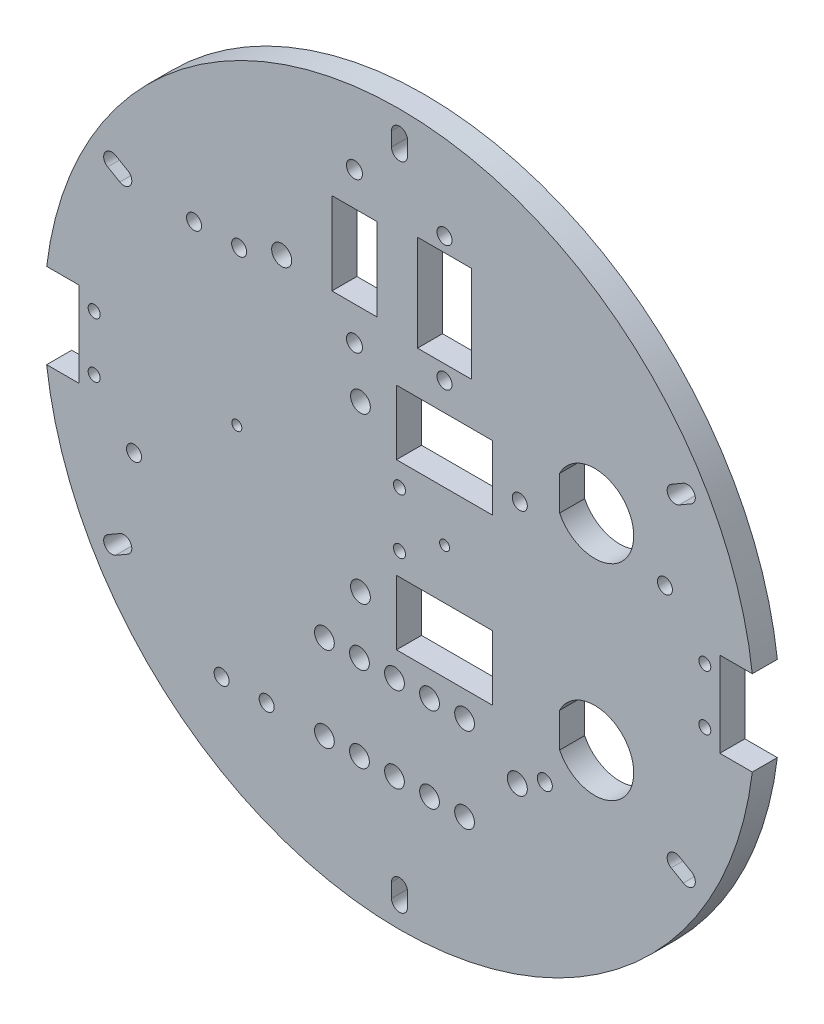
SolidWorks part; units mm, degrees
material "Alliage 1060"
ref_plane "Plan de face" through (0, 0, 0) normal (0, 0, 1) x (1, 0, 0)
ref_plane "Plan de dessus" through (0, 0, 0) normal (0, 1, 0) x (1, 0, 0)
ref_plane "Plan de droite" through (0, 0, 0) normal (1, 0, 0) x (0, 0, -1)
sketch "Esquisse1" plane through (0, 0, 0) normal (0, 0, 1) x (1, 0, 0)
  circle A0 centre (0, 0) radius 71
  dimension "D1" = 142
extrude "Boss.-Extru.1" add sketch "Esquisse1" along normal blind 5
sketch "Esquisse2" plane through (0, 0, 5) normal (0, 0, 1) x (1, 0, 0)
  line L0 (0, 0) -> (0, -76.1453) construction
  line L1 (97.9923, -8.5) -> (64, -8.5)
  line L2 (97.9923, -8.5) -> (97.9923, 8.5)
  line L3 (97.9923, 8.5) -> (64, 8.5)
  line L4 (64, -8.5) -> (64, 8.5)
  line L5 (0, 0) -> (103.2685, 0) construction
  line L7 (-85.8614, -8.5) -> (-64, -8.5)
  line L8 (-85.8614, -8.5) -> (-85.8614, 8.5)
  line L9 (-85.8614, 8.5) -> (-64, 8.5)
  line L10 (-64, -8.5) -> (-64, 8.5)
  dimension "D1" = 128
  dimension "D2" = 17
extrude "Enlèv. mat.-Extru.1" cut sketch "Esquisse2" against normal through all
hole_wizard "Dégagement M21" positions "Esquisse3" profile "Esquisse4" hole size "M2" standard "ISO" end condition through all
sketch "Esquisse3" plane through (0, 0, 0) normal (0, 0, -1) x (-1, 0, 0)
  line L0 (-64, 8.5) -> (-64, -8.5) construction
  line L1 (-64, 0) -> (-80.7851, 0) construction
  point P0 (-61, -5.5)
  dimension "D1" = 3
  dimension "D2" = 5.5
sketch "Esquisse4" plane through (61, -5.5, 0) normal (1, 0, 0) x (0, 1, 0)
  line L0 (0, 0) -> (0, 5)
  line L1 (0, 5) -> (1.2, 5)
  line L2 (1.2, 5) -> (1.2, 0)
  line L5 (1.2, 0) -> (0, 0)
  line L11 (0, -6.35) -> (0, 107.95) construction
  dimension "Diamètre du perçage jusqu'au prochain" = 2.4
  dimension "Profondeur du perçage jusqu'au prochain" = 5
pattern_linear "Répétition linéaire1" count 3 spacing 61 along (-1, 0, 0) count 2 spacing 11 along (0, 1, 0) of "Dégagement M21"
sketch "Esquisse7" plane through (0, 0, 0) normal (0, 0, -1) x (-1, 0, 0)
  line L1 (0, 0) -> (32.5, 0) construction
  circle A0 centre (32.5, 0) radius 1
  dimension "D2" = 2
  dimension "D4" = 32.5
extrude "Enlèv. mat.-Extru.2" cut sketch "Esquisse7" against normal blind 10
sketch "Esquisse8" plane through (0, 0, 5) normal (0, 0, 1) x (1, 0, 0)
  line L0 (32, 23.9409) -> (32, 17.0591)
  line L1 (64, 8.5) -> (64, -8.5) construction
  line L2 (70.4894, 8.5) -> (64, 8.5) construction
  line L3 (64, 0) -> (28.4808, 0) construction
  line L4 (32, -23.9409) -> (32, -17.0591)
  arc A0 (32, 23.9409) -> (32, 17.0591) centre (39, 20.5) cw
  arc A1 (32, -23.9409) -> (32, -17.0591) centre (39, -20.5) ccw
  point P5 (46.8, 20.5)
  dimension "D1" = 7.8
  dimension "D2" = 14.8
  dimension "D3" = 25
  dimension "D4" = 12
extrude "Enlèv. mat.-Extru.3" cut sketch "Esquisse8" against normal through all
hole_wizard "Dégagement M25" positions "Esquisse9" profile "Esquisse10" size "M2" standard "ISO" slot yes end condition through all
sketch "Esquisse9" plane through (0, 0, 5) normal (0, 0, 1) x (1, 0, 0)
  line L0 (0, 0) -> (56.2917, -32.5) construction
  line L2 (0, 0) -> (69.2789, 0) construction
  line L3 (53.6936, -31) -> (58.8897, -34) construction
  point P0 (56.2917, -32.5)
  dimension "D1" = 65
  dimension "D2" = 30
  dimension "D3" = 6
sketch "Esquisse10" plane through (56.2917, -32.5, 5) normal (1, 0, 0) x (0, -1, 0)
  line L0 (0, 0) -> (0, 5)
  line L1 (0, 5) -> (1.6, 5)
  line L2 (1.6, 5) -> (1.6, 0)
  line L5 (1.6, 0) -> (0, 0)
  line L11 (0, -6.35) -> (0, 107.95) construction
  dimension "Diamètre du perçage jusqu'au prochain" = 3.2
  dimension "Profondeur du perçage jusqu'au prochain" = 5
pattern_circular "Répétition circulaire1" count 6 over 360 about axis through (0, 0, 0) along (0, 0, 1) of "Dégagement M25"
sketch "Esquisse11" plane through (0, 0, 0) normal (0, 0, -1) x (-1, 0, 0)
  line L0 (0, 0) -> (-45.0649, 0) construction
  line L1 (-18.6, -10) -> (0.6, -10)
  line L2 (-18.6, -10) -> (-18.6, -22.9)
  line L3 (-18.6, -22.9) -> (0.6, -22.9)
  line L4 (0.6, -10) -> (0.6, -22.9)
  line L5 (0.6, 10) -> (0.6, 22.9)
  line L6 (-18.6, 22.9) -> (0.6, 22.9)
  line L7 (-18.6, 10) -> (-18.6, 22.9)
  line L8 (-18.6, 10) -> (0.6, 10)
  line L9 (22.5124, 41) -> (-32.2474, 41) construction
  line L10 (13.5, 32.75) -> (4.5, 32.75)
  line L11 (13.5, 32.75) -> (13.5, 49.25)
  line L12 (13.5, 49.25) -> (4.5, 49.25)
  line L13 (4.5, 32.75) -> (4.5, 49.25)
  line L14 (9, 56) -> (9, 26) construction
  line L15 (-9, 53.5) -> (-9, 28.5) construction
  line L16 (-18.6, 10) -> (0.6, -10) construction
  line L17 (-14.4, 50.6) -> (-3.6, 50.6)
  line L18 (-14.4, 50.6) -> (-14.4, 31.4)
  line L19 (-14.4, 31.4) -> (-3.6, 31.4)
  line L20 (-3.6, 50.6) -> (-3.6, 31.4)
  line L21 (0.6, 10) -> (-18.6, -10) construction
  circle A0 centre (9, 26) radius 1.6
  circle A1 centre (9, 56) radius 1.6
  circle A2 centre (-9, 28.5) radius 1.5
  circle A3 centre (-9, 53.5) radius 1.5
  circle A4 centre (7.8, 16.45) radius 1.975
  circle A5 centre (7.8, -16.45) radius 1.975
  circle A6 centre (-9, 0) radius 1
  point P27 (4.5, 41)
  point P28 (13.5, 41)
  dimension "D5" = 3.2
  dimension "D6" = 30
  dimension "D9" = 41
  dimension "D10" = 3
  dimension "D16" = 3.95
  dimension "D19" = 2
  dimension "D1" = 19.2
  dimension "D2" = 12.9
  dimension "D3" = 10
  dimension "D4" = 7.8
  dimension "D7" = 9
  dimension "D8" = 25
  dimension "D11" = 16.5
  dimension "D12" = 9
  dimension "D13" = 10.8
  dimension "D14" = 19.2
  dimension "D15" = 9
  dimension "D17" = 6.45
extrude "Enlèv. mat.-Extru.4" cut sketch "Esquisse11" against normal through all
sketch "Esquisse12" plane through (0, 0, 5) normal (0, 0, 1) x (1, 0, 0)
  circle A0 centre (-15, -45) radius 1.975
  dimension "D1" = 3.95
  dimension "D2" = 45
  dimension "D3" = 15
extrude "Enlèv. mat.-Extru.5" cut sketch "Esquisse12" against normal through all
pattern_linear "Répétition linéaire3" count 5 spacing 7 along (1, 0, 0) count 2 spacing 17 along (0, 1, 0) of "Enlèv. mat.-Extru.5"
sketch "Esquisse13" plane through (0, 0, 0) normal (0, 0, -1) x (-1, 0, 0)
  circle A0 centre (23.5374, 33.9599) radius 2
  dimension "D1" = 4
  dimension "D2" = 23.5374
  dimension "D3" = 33.9599
extrude "Enlèv. mat.-Extru.6" cut sketch "Esquisse13" against normal through all
pattern_circular "Répétition circulaire2" count 2 over 360 about axis through (0, 0, 5) along (0, 0, 1) of "Enlèv. mat.-Extru.6" reverse direction yes
sketch "Esquisse15" plane through (0, 0, 5) normal (0, 0, 1) x (1, 0, 0)
  circle A0 centre (53.035, 15.0401) radius 1.5
  circle A1 centre (24.035, 15.0401) radius 1.5
  circle A2 centre (29.035, -30.9599) radius 1.5
  circle A3 centre (-35.5374, -45.0401) radius 1.5
  circle A4 centre (-26.5374, -45.0401) radius 1.5
  circle A5 centre (-41.0374, 30.9599) radius 1.5
  circle A6 centre (-32.0374, 30.9599) radius 1.5
  circle A7 centre (-53.0374, -15.0401) radius 1.5
  dimension "D1" = 3
  dimension "D2" = 3
  dimension "D3" = 3
  dimension "D4" = 3
  dimension "D5" = 3
  dimension "D6" = 3
  dimension "D7" = 3
  dimension "D8" = 3
extrude "Enlèv. mat.-Extru.8" cut sketch "Esquisse15" against normal blind 10
